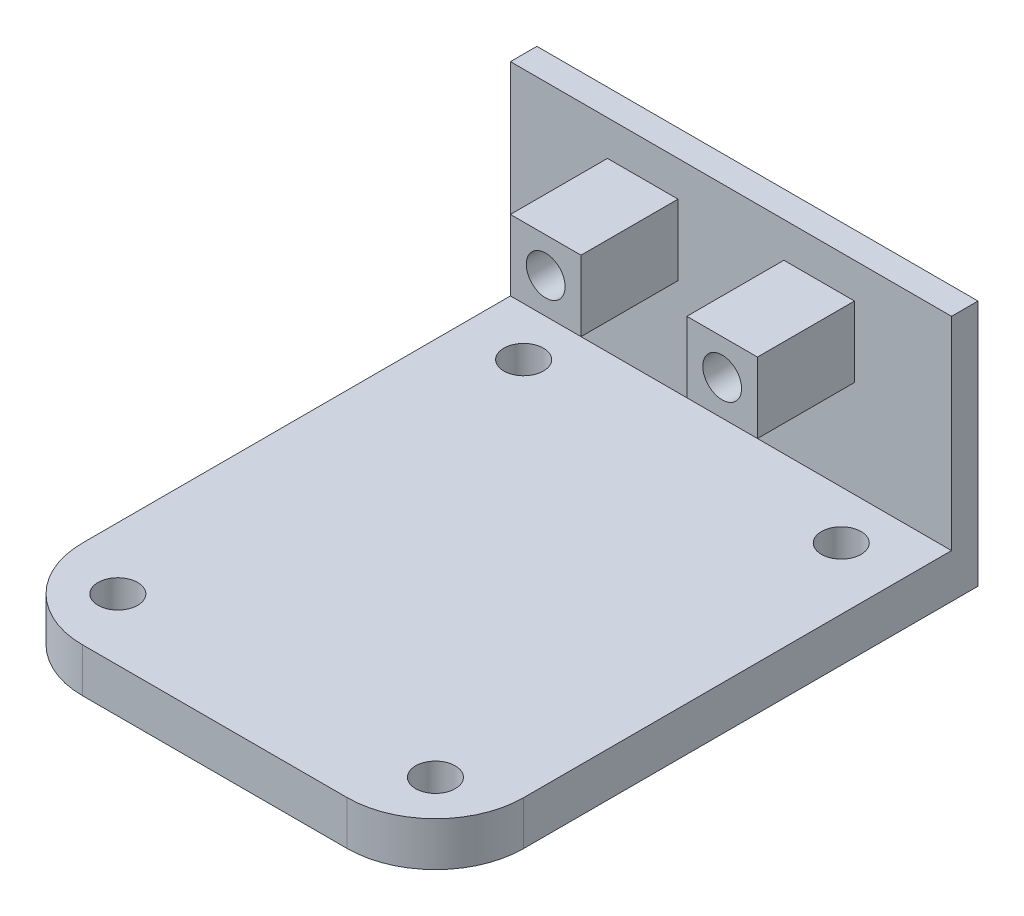
SolidWorks part; units mm, degrees
ref_plane "Front Plane" through (0, 0, 0) normal (0, 0, 1) x (1, 0, 0)
ref_plane "Top Plane" through (0, 0, 0) normal (0, 1, 0) x (1, 0, 0)
ref_plane "Right Plane" through (0, 0, 0) normal (1, 0, 0) x (0, 0, -1)
sketch "Sketch1" plane through (0, 0, 0) normal (0, 0, 1) x (1, 0, 0)
  line L1 (-25, 16.5) -> (25, 16.5)
  line L2 (-25, 16.5) -> (-25, -16.5)
  line L3 (-25, -16.5) -> (25, -16.5)
  line L4 (25, 16.5) -> (25, -16.5)
  line L5 (-25, 16.5) -> (25, -16.5) construction
  line L6 (-25, -16.5) -> (25, 16.5) construction
  point P0 (0, 0)
  dimension "D1" = 33
  dimension "D2" = 50
extrude "Boss-Extrude1" add sketch "Sketch1" along normal blind 3 contours L2 L3 L4 L1
sketch "Sketch2" plane through (0, 0, 3) normal (0, 0, 1) x (1, 0, 0)
  line L0 (25, 16.5) -> (25, -16.5) construction
  line L1 (-25, -16.5) -> (25, -16.5)
  line L2 (-25, -16.5) -> (-25, -11.5)
  line L3 (-25, -11.5) -> (25, -11.5)
  line L4 (25, -16.5) -> (25, -11.5)
  dimension "D1" = 5
extrude "Boss-Extrude2" add sketch "Sketch2" along normal blind 58.5
sketch "Sketch3" plane through (0, -11.5, 0) normal (0, 1, 0) x (1, 0, 0)
  line L0 (-25, -51.5) -> (-25, -61.5)
  line L1 (-25, -61.5) -> (-15, -61.5)
  line L2 (15, -61.5) -> (25, -61.5)
  line L3 (25, -61.5) -> (25, -51.5)
  arc A1 (15, -61.5) -> (25, -51.5) centre (15, -51.5) ccw construction
  arc A2 (15, -61.5) -> (25, -51.5) centre (15, -51.5) ccw
  arc A3 (-25, -51.5) -> (-15, -61.5) centre (-15, -51.5) ccw construction
  arc A4 (-25, -51.5) -> (-15, -61.5) centre (-15, -51.5) ccw
  circle A5 centre (-18, -54.5) radius 2.2479 construction
  circle A6 centre (-18, -54.5) radius 2.2479
  circle A7 centre (18, -54.5) radius 2.2479 construction
  circle A8 centre (18, -54.5) radius 2.2479
  circle A9 centre (-18, -8.5) radius 2.2479 construction
  circle A10 centre (-18, -8.5) radius 2.2479
  circle A11 centre (18, -8.5) radius 2.2479 construction
  circle A12 centre (18, -8.5) radius 2.2479
extrude "Cut-Extrude1" cut sketch "Sketch3" against normal up to surface (5 mm away) up to face at (0, -16.5, 30.75)
sketch "Sketch4" plane through (0, 0, 3) normal (0, 0, 1) x (1, 0, 0)
  line L5 (-14.0006, 7.5) -> (-6.0006, 7.5)
  line L6 (-14.0006, 7.5) -> (-14.0006, -0.5)
  line L7 (-14.0006, -0.5) -> (-6.0006, -0.5)
  line L8 (-6.0006, 7.5) -> (-6.0006, -0.5)
  line L9 (-14.0006, 7.5) -> (-6.0006, -0.5) construction
  line L10 (-14.0006, -0.5) -> (-6.0006, 7.5) construction
  line L11 (5.9994, 7.5) -> (13.9994, 7.5)
  line L12 (5.9994, 7.5) -> (5.9994, -0.5)
  line L13 (5.9994, -0.5) -> (13.9994, -0.5)
  line L14 (13.9994, 7.5) -> (13.9994, -0.5)
  line L15 (5.9994, 7.5) -> (13.9994, -0.5) construction
  line L16 (5.9994, -0.5) -> (13.9994, 7.5) construction
  circle A0 centre (-10.0006, 3.5) radius 2.2 construction
  circle A1 centre (-10.0006, 3.5) radius 2.2
  circle A2 centre (9.9994, 3.5) radius 2.2 construction
  circle A3 centre (9.9994, 3.5) radius 2.2
  dimension "D1" = 8
extrude "Boss-Extrude3" add sketch "Sketch4" along normal blind 11
sketch "Sketch5" plane through (0, 0, 14) normal (0, 0, 1) x (1, 0, 0)
  circle A0 centre (9.9994, 3.5) radius 2.2 construction
  circle A1 centre (9.9994, 3.5) radius 2.2
  circle A2 centre (-10.0006, 3.5) radius 2.2 construction
  circle A3 centre (-10.0006, 3.5) radius 2.2
extrude "Cut-Extrude2" cut sketch "Sketch5" against normal up to surface (14 mm away) up to face at (0, 0, 0)
sketch "Sketch6" plane through (0, 0, 3) normal (0, 0, 1) x (1, 0, 0)
  line L0 (25, 16.5) -> (25, -11.5) construction
  line L1 (-25, 16.5) -> (25, 16.5)
  line L2 (-25, 16.5) -> (-25, 11.5)
  line L3 (-25, 11.5) -> (25, 11.5)
  line L4 (25, 16.5) -> (25, 11.5)
  dimension "D1" = 5
extrude "Cut-Extrude3" cut sketch "Sketch6" against normal up to surface (3 mm away) up to face at (7.7994, 3.5, 0)
